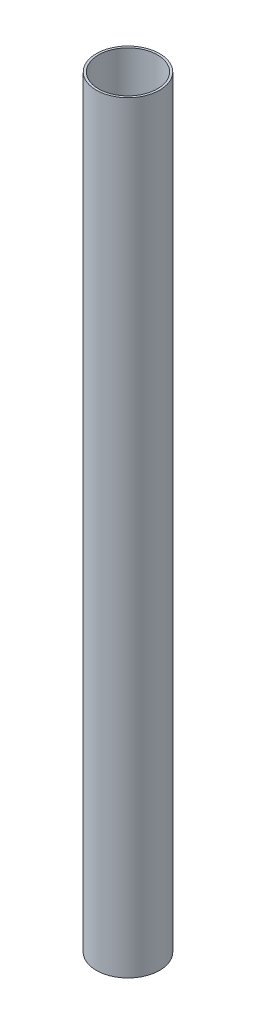
SolidWorks part; units mm, degrees
ref_plane "Front Plane" through (0, 0, 0) normal (0, 0, 1) x (1, 0, 0)
ref_plane "Top Plane" through (0, 0, 0) normal (0, 1, 0) x (1, 0, 0)
ref_plane "Right Plane" through (0, 0, 0) normal (1, 0, 0) x (0, 0, -1)
sketch "driver" plane through (0, 0, 0) normal (0, 1, 0) x (1, 0, 0)
  circle A0 centre (0, 0) radius 29.083
  circle A1 centre (0, 0) radius 27.0675
  circle A2 centre (0, 0) radius 20.6
  circle A3 centre (0, 0) radius 19
  dimension "D1" = 58.166
  dimension "D2" = 54.135
  dimension "D3" = 38
  dimension "D4" = 1.6
extrude "aero" add sketch "driver" along normal blind 700 contours A0 A1 region at (-28.2604, 0, 0)
extrude "motor" add sketch "driver<3>" along normal blind 600 separate body contours A2 A3 region at (-20.0173, 0, 0)
sketch "driver<3>" plane through (0, 0, 0) normal (0, 1, 0) x (1, 0, 0) same geometry as "driver"
